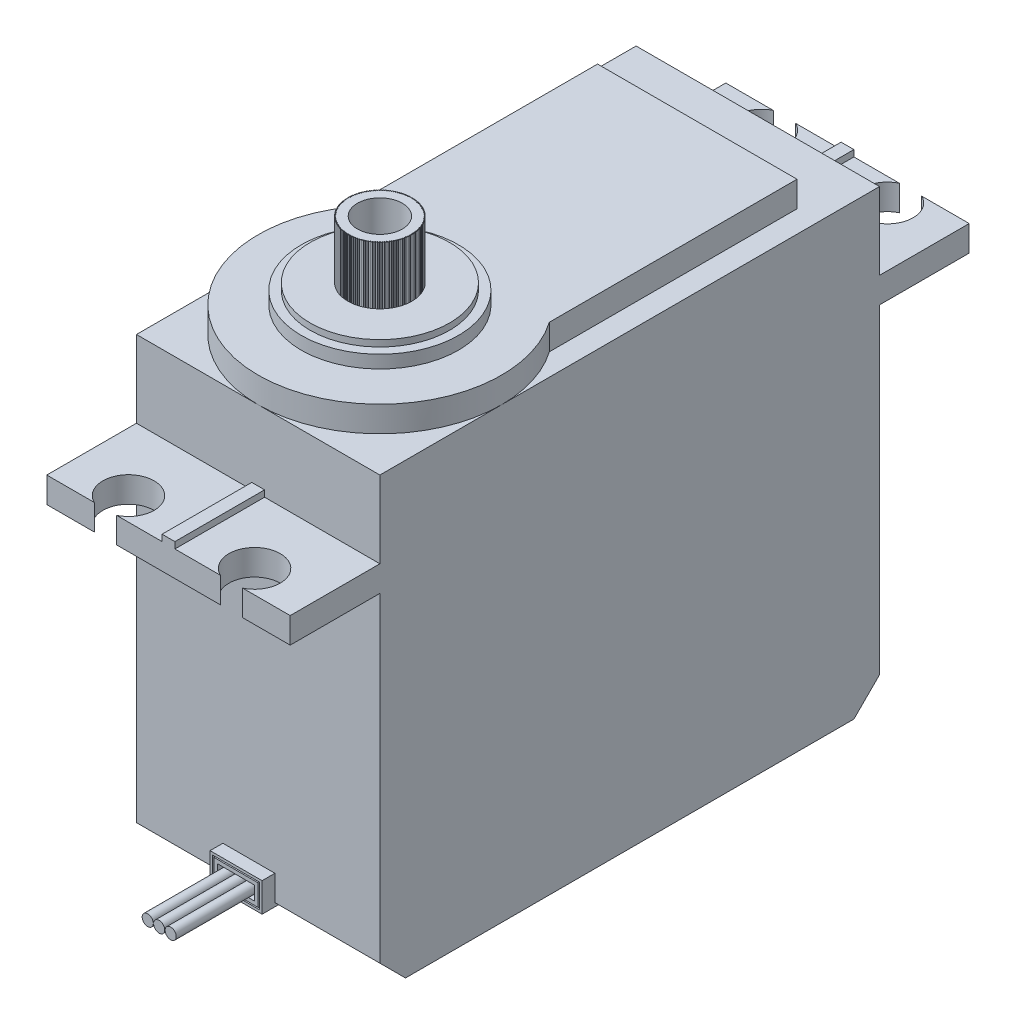
SolidWorks part; units mm, degrees
material "ABS PC"
ref_plane "Front Plane" through (0, 0, 0) normal (0, 0, 1) x (1, 0, 0)
ref_plane "Top Plane" through (0, 0, 0) normal (0, 1, 0) x (1, 0, 0)
ref_plane "Right Plane" through (0, 0, 0) normal (1, 0, 0) x (0, 0, -1)
sketch "Sketch1" plane through (0, 0, 0) normal (0, 1, 0) x (1, 0, 0)
  line L0 (0, 0) -> (19, 0)
  line L1 (19, 0) -> (19, 39)
  line L2 (19, 39) -> (0, 39)
  line L3 (0, 39) -> (0, 0)
  dimension "D1" = 19
  dimension "D2" = 39
extrude "Boss-Extrude1" add sketch "Sketch1" along normal blind 35
sketch "Sketch2" plane through (0, 35, 0) normal (0, 1, 0) x (1, 0, 0)
  line L0 (0, 39) -> (0, 0) construction
  line L2 (17.2849, 14.9447) -> (17.2849, 34.2756)
  line L3 (17.2849, 34.2756) -> (1.7151, 34.2756)
  line L5 (1.7151, 14.9447) -> (1.7151, 34.2756)
  circle A0 centre (9.5, 9.5) radius 1.75
  circle A1 centre (9.5, 9.5) radius 2.5
  circle A2 centre (9.5, 9.5) radius 9.5
  circle A3 centre (9.5, 9.5) radius 6.134
  circle A4 centre (9.5, 9.5) radius 5.4447
  dimension "D2" = 3.5
  dimension "D3" = 5
  dimension "D4" = 12.2681
  dimension "D1" = 10.8894
  dimension "D5" = 19
  dimension "D6" = 1.7151
  dimension "D7" = 9.5
  dimension "D8" = 9.5
  dimension "D10" = 34.2756
extrude "Boss-Extrude2" add sketch "Sketch2" along normal blind 2 contours A2 L2 L3 L5 | A2 A3 region at (9.5, 35, -25.9923) region at (18.3048, 35, -12.2735)
extrude "Boss-Extrude3" add sketch "Sketch2<4>" along normal blind 3 contours A3 A4 region at (3.5394, 35, -9.5)
sketch "Sketch2<4>" plane through (0, 35, 0) normal (0, 1, 0) x (1, 0, 0) same geometry as "Sketch2"
extrude "Boss-Extrude4" add sketch "Sketch2<5>" along normal blind 3.5 contours A4 A1 region at (4.2093, 35, -9.5)
sketch "Sketch2<5>" plane through (0, 35, 0) normal (0, 1, 0) x (1, 0, 0) same geometry as "Sketch2"
extrude "Boss-Extrude5" add sketch "Sketch2<6>" along normal blind 8 contours A1 A0 region at (7.0707, 35, -9.5)
sketch "Sketch2<6>" plane through (0, 35, 0) normal (0, 1, 0) x (1, 0, 0) same geometry as "Sketch2"
ref_plane "Plane1" through (0, 27, 0) normal (0, 1, 0) x (1, 0, 0)
sketch "Sketch3" plane through (0, 27, 0) normal (0, 1, 0) x (1, 0, 0)
  line L0 (0, 39) -> (19, 39)
  line L1 (19, 39) -> (19, 46)
  line L2 (19, 46) -> (15.2942, 46)
  line L3 (0, 46) -> (0, 39)
  line L4 (0, 0) -> (19, 0)
  line L5 (13.5465, 46) -> (5.4535, 46)
  line L6 (3.7058, 46) -> (0, 46)
  line L7 (0, 39) -> (0, 19.5)
  line L8 (0, 39) -> (0, 9.5) construction
  line L9 (0, 19.5) -> (19, 19.5)
  line L10 (19, 9.5) -> (19, 39) construction
  line L11 (9.5, 46) -> (9, 46)
  line L12 (9, 46) -> (9, 39)
  line L13 (9, 39) -> (10, 39)
  line L14 (10, 39) -> (10, 46)
  line L15 (19, 0) -> (19, -7)
  line L16 (19, -7) -> (15.2942, -7)
  line L17 (10, 0) -> (10, -7)
  line L18 (9, -7) -> (9, 0)
  line L19 (13.5465, -7) -> (5.4535, -7)
  line L20 (3.7058, -7) -> (0, -7)
  line L21 (0, -7) -> (0, 0)
  arc A0 (13.5465, 46) -> (15.2942, 46) centre (14.4204, 44.201) ccw
  arc A1 (5.4535, 46) -> (3.7058, 46) centre (4.5796, 44.201) cw
  arc A2 (13.5465, -7) -> (15.2942, -7) centre (14.4204, -5.201) cw
  arc A3 (5.4535, -7) -> (3.7058, -7) centre (4.5796, -5.201) ccw
  point P7 (0, 0)
  dimension "D2" = 4
  dimension "D1" = 7
  dimension "D3" = 19.5
  dimension "D4" = 0.5
  dimension "D5" = 1
extrude "Boss-Extrude6" add sketch "Sketch3" along normal blind 2 contours A3 L19 L18 L4 L21 L20 | L19 A2 L16 L15 L4 L17 | A0 L5 L14 L0 L1 L2 | L5 A1 L6 L3 L0 L12 region at (4.4806, 27, -42.0949) region at (14.5194, 27, -42.0949) region at (4.4806, 27, 3.0949) region at (14.5194, 27, 3.0949)
extrude "Boss-Extrude7" add sketch "Sketch3<3>" along normal blind 2.5 contours L0 L14 L5 L12 | L19 L17 L4 L18 region at (9.5, 27, -42.5) region at (9.5, 27, 3.5)
sketch "Sketch3<3>" plane through (0, 27, 0) normal (0, 1, 0) x (1, 0, 0) same geometry as "Sketch3"
ref_plane "Plane2" through (0, 0, -7) normal (0, 0, 1) x (1, 0, 0)
sketch "Sketch5" plane through (0, 43, 0) normal (0, 1, 0) x (1, 0, 0)
  line L0 (9.5017, 7) -> (9.5017, 7.0748) construction
  line L1 (-6.6, 7) -> (6.6, 7) construction
  line L2 (9.5017, 7.0748) -> (9.4463, 7.0077)
  line L3 (9.5017, 7.0748) -> (9.5593, 7.0077)
  line L4 (9.3748, 7.078) -> (9.4288, 7.008)
  line L5 (9.3748, 7.078) -> (9.3159, 7.0139)
  line L6 (9.2482, 7.0879) -> (9.2985, 7.0151)
  line L7 (9.2482, 7.0879) -> (9.1861, 7.027)
  line L8 (9.1223, 7.1044) -> (9.1687, 7.0291)
  line L9 (9.1223, 7.1044) -> (9.0571, 7.0468)
  line L10 (8.9975, 7.1274) -> (9.0399, 7.0498)
  line L11 (8.9975, 7.1274) -> (8.9293, 7.0733)
  line L12 (8.874, 7.157) -> (8.9123, 7.0773)
  line L13 (8.874, 7.157) -> (8.8031, 7.1065)
  line L14 (8.7522, 7.1929) -> (8.7863, 7.1113)
  line L15 (8.7522, 7.1929) -> (8.6788, 7.1463)
  line L16 (8.6325, 7.2352) -> (8.6622, 7.152)
  line L17 (8.6325, 7.2352) -> (8.5567, 7.1925)
  line L18 (8.5152, 7.2837) -> (8.5405, 7.199)
  line L19 (8.5152, 7.2837) -> (8.4372, 7.245)
  line L20 (8.4005, 7.3383) -> (8.4214, 7.2524)
  line L21 (8.4005, 7.3383) -> (8.3207, 7.3037)
  line L22 (8.2889, 7.3988) -> (8.3052, 7.3119)
  line L23 (8.2889, 7.3988) -> (8.2073, 7.3684)
  line L24 (8.1806, 7.4651) -> (8.1924, 7.3775)
  line L25 (8.1806, 7.4651) -> (8.0976, 7.439)
  line L26 (8.0759, 7.5369) -> (8.0831, 7.4488)
  line L27 (8.0759, 7.5369) -> (7.9916, 7.5152)
  line L28 (7.9751, 7.6142) -> (7.9777, 7.5258)
  line L29 (7.9751, 7.6142) -> (7.8898, 7.5969)
  line L30 (7.8785, 7.6965) -> (7.8764, 7.6081)
  line L31 (7.8785, 7.6965) -> (7.7924, 7.6838)
  line L32 (7.7863, 7.7839) -> (7.7796, 7.6957)
  line L33 (7.7863, 7.7839) -> (7.6997, 7.7756)
  line L34 (7.6989, 7.8759) -> (7.6876, 7.7882)
  line L35 (7.6989, 7.8759) -> (7.6119, 7.8722)
  line L36 (7.6163, 7.9724) -> (7.6005, 7.8854)
  line L37 (7.6163, 7.9724) -> (7.5293, 7.9733)
  line L38 (7.539, 8.0731) -> (7.5186, 7.987)
  line L39 (7.539, 8.0731) -> (7.4521, 8.0785)
  line L40 (7.467, 8.1777) -> (7.4421, 8.0928)
  line L41 (7.467, 8.1777) -> (7.3805, 8.1876)
  line L42 (7.4006, 8.2859) -> (7.3713, 8.2025)
  line L43 (7.4006, 8.2859) -> (7.3148, 8.3003)
  line L44 (7.3399, 8.3974) -> (7.3063, 8.3156)
  line L45 (7.3399, 8.3974) -> (7.255, 8.4163)
  line L46 (7.2852, 8.512) -> (7.2473, 8.4321)
  line L47 (7.2852, 8.512) -> (7.2013, 8.5353)
  line L48 (7.2365, 8.6293) -> (7.1945, 8.5514)
  line L49 (7.2365, 8.6293) -> (7.154, 8.657)
  line L50 (7.194, 8.7489) -> (7.148, 8.6734)
  line L51 (7.194, 8.7489) -> (7.1131, 8.7809)
  line L52 (7.1579, 8.8706) -> (7.108, 8.7976)
  line L53 (7.1579, 8.8706) -> (7.0787, 8.9068)
  line L54 (7.1281, 8.9941) -> (7.0745, 8.9238)
  line L55 (7.1281, 8.9941) -> (7.051, 9.0343)
  line L56 (7.1049, 9.1189) -> (7.0477, 9.0515)
  line L57 (7.1049, 9.1189) -> (7.03, 9.1631)
  line L58 (7.0882, 9.2448) -> (7.0275, 9.1805)
  line L59 (7.0882, 9.2448) -> (7.0157, 9.2929)
  line L60 (7.0782, 9.3713) -> (7.0142, 9.3103)
  line L61 (7.0782, 9.3713) -> (7.0083, 9.4232)
  line L62 (7.0748, 9.4983) -> (7.0077, 9.4407)
  line L63 (7.0748, 9.4983) -> (7.0077, 9.5537)
  line L64 (7.078, 9.6252) -> (7.008, 9.5712)
  line L65 (7.078, 9.6252) -> (7.0139, 9.6841)
  line L66 (7.0879, 9.7518) -> (7.0151, 9.7015)
  line L67 (7.0879, 9.7518) -> (7.027, 9.8139)
  line L68 (7.1044, 9.8777) -> (7.0291, 9.8313)
  line L69 (7.1044, 9.8777) -> (7.0468, 9.9429)
  line L70 (7.1274, 10.0025) -> (7.0498, 9.9601)
  line L71 (7.1274, 10.0025) -> (7.0733, 10.0707)
  line L72 (7.157, 10.126) -> (7.0773, 10.0877)
  line L73 (7.157, 10.126) -> (7.1065, 10.1969)
  line L74 (7.1929, 10.2478) -> (7.1113, 10.2137)
  line L75 (7.1929, 10.2478) -> (7.1463, 10.3212)
  line L76 (7.2352, 10.3675) -> (7.152, 10.3378)
  line L77 (7.2352, 10.3675) -> (7.1925, 10.4433)
  line L78 (7.2837, 10.4848) -> (7.199, 10.4595)
  line L79 (7.2837, 10.4848) -> (7.245, 10.5628)
  line L80 (7.3383, 10.5995) -> (7.2524, 10.5786)
  line L81 (7.3383, 10.5995) -> (7.3037, 10.6793)
  line L82 (7.3988, 10.7111) -> (7.3119, 10.6948)
  line L83 (7.3988, 10.7111) -> (7.3684, 10.7927)
  line L84 (7.4651, 10.8194) -> (7.3775, 10.8076)
  line L85 (7.4651, 10.8194) -> (7.439, 10.9024)
  line L86 (7.5369, 10.9241) -> (7.4488, 10.9169)
  line L87 (7.5369, 10.9241) -> (7.5152, 11.0084)
  line L88 (7.6142, 11.0249) -> (7.5258, 11.0223)
  line L89 (7.6142, 11.0249) -> (7.5969, 11.1102)
  line L90 (7.6965, 11.1215) -> (7.6081, 11.1236)
  line L91 (7.6965, 11.1215) -> (7.6838, 11.2076)
  line L92 (7.7839, 11.2137) -> (7.6957, 11.2204)
  line L93 (7.7839, 11.2137) -> (7.7756, 11.3003)
  line L94 (7.8759, 11.3011) -> (7.7882, 11.3124)
  line L95 (7.8759, 11.3011) -> (7.8722, 11.3881)
  line L96 (7.9724, 11.3837) -> (7.8854, 11.3995)
  line L97 (7.9724, 11.3837) -> (7.9733, 11.4707)
  line L98 (8.0731, 11.461) -> (7.987, 11.4814)
  line L99 (8.0731, 11.461) -> (8.0785, 11.5479)
  line L100 (8.1777, 11.533) -> (8.0928, 11.5579)
  line L101 (8.1777, 11.533) -> (8.1876, 11.6195)
  line L102 (8.2859, 11.5994) -> (8.2025, 11.6287)
  line L103 (8.2859, 11.5994) -> (8.3003, 11.6852)
  line L104 (8.3974, 11.6601) -> (8.3156, 11.6937)
  line L105 (8.3974, 11.6601) -> (8.4163, 11.745)
  line L106 (8.512, 11.7148) -> (8.4321, 11.7527)
  line L107 (8.512, 11.7148) -> (8.5353, 11.7987)
  line L108 (8.6293, 11.7635) -> (8.5514, 11.8055)
  line L109 (8.6293, 11.7635) -> (8.657, 11.846)
  line L110 (8.7489, 11.806) -> (8.6734, 11.852)
  line L111 (8.7489, 11.806) -> (8.7809, 11.8869)
  line L112 (8.8706, 11.8421) -> (8.7976, 11.892)
  line L113 (8.8706, 11.8421) -> (8.9068, 11.9213)
  line L114 (8.9941, 11.8719) -> (8.9238, 11.9255)
  line L115 (8.9941, 11.8719) -> (9.0343, 11.949)
  line L116 (9.1189, 11.8951) -> (9.0515, 11.9523)
  line L117 (9.1189, 11.8951) -> (9.1631, 11.97)
  line L118 (9.2448, 11.9118) -> (9.1805, 11.9725)
  line L119 (9.2448, 11.9118) -> (9.2929, 11.9843)
  line L120 (9.3713, 11.9218) -> (9.3103, 11.9858)
  line L121 (9.3713, 11.9218) -> (9.4232, 11.9917)
  line L122 (9.4983, 11.9252) -> (9.4407, 11.9923)
  line L123 (9.4983, 11.9252) -> (9.5537, 11.9923)
  line L124 (9.6252, 11.922) -> (9.5712, 11.992)
  line L125 (9.6252, 11.922) -> (9.6841, 11.9861)
  line L126 (9.7518, 11.9121) -> (9.7015, 11.9849)
  line L127 (9.7518, 11.9121) -> (9.8139, 11.973)
  line L128 (9.8777, 11.8956) -> (9.8313, 11.9709)
  line L129 (9.8777, 11.8956) -> (9.9429, 11.9532)
  line L130 (10.0025, 11.8726) -> (9.9601, 11.9502)
  line L131 (10.0025, 11.8726) -> (10.0707, 11.9267)
  line L132 (10.126, 11.843) -> (10.0877, 11.9227)
  line L133 (10.126, 11.843) -> (10.1969, 11.8935)
  line L134 (10.2478, 11.8071) -> (10.2137, 11.8887)
  line L135 (10.2478, 11.8071) -> (10.3212, 11.8537)
  line L136 (10.3675, 11.7648) -> (10.3378, 11.848)
  line L137 (10.3675, 11.7648) -> (10.4433, 11.8075)
  line L138 (10.4848, 11.7163) -> (10.4595, 11.801)
  line L139 (10.4848, 11.7163) -> (10.5628, 11.755)
  line L140 (10.5995, 11.6617) -> (10.5786, 11.7476)
  line L141 (10.5995, 11.6617) -> (10.6793, 11.6963)
  line L142 (10.7111, 11.6012) -> (10.6948, 11.6881)
  line L143 (10.7111, 11.6012) -> (10.7927, 11.6316)
  line L144 (10.8194, 11.5349) -> (10.8076, 11.6225)
  line L145 (10.8194, 11.5349) -> (10.9024, 11.561)
  line L146 (10.9241, 11.4631) -> (10.9169, 11.5512)
  line L147 (10.9241, 11.4631) -> (11.0084, 11.4848)
  line L148 (11.0249, 11.3858) -> (11.0223, 11.4742)
  line L149 (11.0249, 11.3858) -> (11.1102, 11.4031)
  line L150 (11.1215, 11.3035) -> (11.1236, 11.3919)
  line L151 (11.1215, 11.3035) -> (11.2076, 11.3162)
  line L152 (11.2137, 11.2161) -> (11.2204, 11.3043)
  line L153 (11.2137, 11.2161) -> (11.3003, 11.2244)
  line L154 (11.3011, 11.1241) -> (11.3124, 11.2118)
  line L155 (11.3011, 11.1241) -> (11.3881, 11.1278)
  line L156 (11.3837, 11.0276) -> (11.3995, 11.1146)
  line L157 (11.3837, 11.0276) -> (11.4707, 11.0267)
  line L158 (11.461, 10.9269) -> (11.4814, 11.013)
  line L159 (11.461, 10.9269) -> (11.5479, 10.9215)
  line L160 (11.533, 10.8223) -> (11.5579, 10.9072)
  line L161 (11.533, 10.8223) -> (11.6195, 10.8124)
  line L162 (11.5994, 10.7141) -> (11.6287, 10.7975)
  line L163 (11.5994, 10.7141) -> (11.6852, 10.6997)
  line L164 (11.6601, 10.6026) -> (11.6937, 10.6844)
  line L165 (11.6601, 10.6026) -> (11.745, 10.5837)
  line L166 (11.7148, 10.488) -> (11.7527, 10.5679)
  line L167 (11.7148, 10.488) -> (11.7987, 10.4647)
  line L168 (11.7635, 10.3707) -> (11.8055, 10.4486)
  line L169 (11.7635, 10.3707) -> (11.846, 10.343)
  line L170 (11.806, 10.2511) -> (11.852, 10.3266)
  line L171 (11.806, 10.2511) -> (11.8869, 10.2191)
  line L172 (11.8421, 10.1294) -> (11.892, 10.2024)
  line L173 (11.8421, 10.1294) -> (11.9213, 10.0932)
  line L174 (11.8719, 10.0059) -> (11.9255, 10.0762)
  line L175 (11.8719, 10.0059) -> (11.949, 9.9657)
  line L176 (11.8951, 9.8811) -> (11.9523, 9.9485)
  line L177 (11.8951, 9.8811) -> (11.97, 9.8369)
  line L178 (11.9118, 9.7552) -> (11.9725, 9.8195)
  line L179 (11.9118, 9.7552) -> (11.9843, 9.7071)
  line L180 (11.9218, 9.6287) -> (11.9858, 9.6897)
  line L181 (11.9218, 9.6287) -> (11.9917, 9.5768)
  line L182 (11.9252, 9.5017) -> (11.9923, 9.5593)
  line L183 (11.9252, 9.5017) -> (11.9923, 9.4463)
  line L184 (11.922, 9.3748) -> (11.992, 9.4288)
  line L185 (11.922, 9.3748) -> (11.9861, 9.3159)
  line L186 (11.9121, 9.2482) -> (11.9849, 9.2985)
  line L187 (11.9121, 9.2482) -> (11.973, 9.1861)
  line L188 (11.8956, 9.1223) -> (11.9709, 9.1687)
  line L189 (11.8956, 9.1223) -> (11.9532, 9.0571)
  line L190 (11.8726, 8.9975) -> (11.9502, 9.0399)
  line L191 (11.8726, 8.9975) -> (11.9267, 8.9293)
  line L192 (11.843, 8.874) -> (11.9227, 8.9123)
  line L193 (11.843, 8.874) -> (11.8935, 8.8031)
  line L194 (11.8071, 8.7522) -> (11.8887, 8.7863)
  line L195 (11.8071, 8.7522) -> (11.8537, 8.6788)
  line L196 (11.7648, 8.6325) -> (11.848, 8.6622)
  line L197 (11.7648, 8.6325) -> (11.8075, 8.5567)
  line L198 (11.7163, 8.5152) -> (11.801, 8.5405)
  line L199 (11.7163, 8.5152) -> (11.755, 8.4372)
  line L200 (11.6617, 8.4005) -> (11.7476, 8.4214)
  line L201 (11.6617, 8.4005) -> (11.6963, 8.3207)
  line L202 (11.6012, 8.2889) -> (11.6881, 8.3052)
  line L203 (11.6012, 8.2889) -> (11.6316, 8.2073)
  line L204 (11.5349, 8.1806) -> (11.6225, 8.1924)
  line L205 (11.5349, 8.1806) -> (11.561, 8.0976)
  line L206 (11.4631, 8.0759) -> (11.5512, 8.0831)
  line L207 (11.4631, 8.0759) -> (11.4848, 7.9916)
  line L208 (11.3858, 7.9751) -> (11.4742, 7.9777)
  line L209 (11.3858, 7.9751) -> (11.4031, 7.8898)
  line L210 (11.3035, 7.8785) -> (11.3919, 7.8764)
  line L211 (11.3035, 7.8785) -> (11.3162, 7.7924)
  line L212 (11.2161, 7.7863) -> (11.3043, 7.7796)
  line L213 (11.2161, 7.7863) -> (11.2244, 7.6997)
  line L214 (11.1241, 7.6989) -> (11.2118, 7.6876)
  line L215 (11.1241, 7.6989) -> (11.1278, 7.6119)
  line L216 (11.0276, 7.6163) -> (11.1146, 7.6005)
  line L217 (11.0276, 7.6163) -> (11.0267, 7.5293)
  line L218 (10.9269, 7.539) -> (11.013, 7.5186)
  line L219 (10.9269, 7.539) -> (10.9215, 7.4521)
  line L220 (10.8223, 7.467) -> (10.9072, 7.4421)
  line L221 (10.8223, 7.467) -> (10.8124, 7.3805)
  line L222 (10.7141, 7.4006) -> (10.7975, 7.3713)
  line L223 (10.7141, 7.4006) -> (10.6997, 7.3148)
  line L224 (10.6026, 7.3399) -> (10.6844, 7.3063)
  line L225 (10.6026, 7.3399) -> (10.5837, 7.255)
  line L226 (10.488, 7.2852) -> (10.5679, 7.2473)
  line L227 (10.488, 7.2852) -> (10.4647, 7.2013)
  line L228 (10.3707, 7.2365) -> (10.4486, 7.1945)
  line L229 (10.3707, 7.2365) -> (10.343, 7.154)
  line L230 (10.2511, 7.194) -> (10.3266, 7.148)
  line L231 (10.2511, 7.194) -> (10.2191, 7.1131)
  line L232 (10.1294, 7.1579) -> (10.2024, 7.108)
  line L233 (10.1294, 7.1579) -> (10.0932, 7.0787)
  line L234 (10.0059, 7.1281) -> (10.0762, 7.0745)
  line L235 (10.0059, 7.1281) -> (9.9657, 7.051)
  line L236 (9.8811, 7.1049) -> (9.9485, 7.0477)
  line L237 (9.8811, 7.1049) -> (9.8369, 7.03)
  line L238 (9.7552, 7.0882) -> (9.8195, 7.0275)
  line L239 (9.7552, 7.0882) -> (9.7071, 7.0157)
  line L240 (9.6287, 7.0782) -> (9.6897, 7.0142)
  line L241 (9.6287, 7.0782) -> (9.5768, 7.0083)
  line L242 (9.5, 9.5) -> (9.5028, 7.2027) construction
  arc A0 (9.5593, 7.0077) -> (9.4463, 7.0077) centre (9.5028, 7.2027) cw
  arc A1 (9.4288, 7.008) -> (9.3159, 7.0139) centre (9.3826, 7.2057) cw
  arc A2 (9.2985, 7.0151) -> (9.1861, 7.027) centre (9.2627, 7.215) cw
  arc A3 (9.1687, 7.0291) -> (9.0571, 7.0468) centre (9.1434, 7.2305) cw
  arc A4 (9.0399, 7.0498) -> (8.9293, 7.0733) centre (9.0251, 7.2523) cw
  arc A5 (8.9123, 7.0773) -> (8.8031, 7.1065) centre (8.9081, 7.2802) cw
  arc A6 (8.7863, 7.1113) -> (8.6788, 7.1463) centre (8.7928, 7.3143) cw
  arc A7 (8.6622, 7.152) -> (8.5567, 7.1925) centre (8.6794, 7.3543) cw
  arc A8 (8.5405, 7.199) -> (8.4372, 7.245) centre (8.5682, 7.4001) cw
  arc A9 (8.4214, 7.2524) -> (8.3207, 7.3037) centre (8.4596, 7.4518) cw
  arc A10 (8.3052, 7.3119) -> (8.2073, 7.3684) centre (8.3538, 7.5091) cw
  arc A11 (8.1924, 7.3775) -> (8.0976, 7.439) centre (8.2512, 7.5718) cw
  arc A12 (8.0831, 7.4488) -> (7.9916, 7.5152) centre (8.152, 7.6398) cw
  arc A13 (7.9777, 7.5258) -> (7.8898, 7.5969) centre (8.0565, 7.7129) cw
  arc A14 (7.8764, 7.6081) -> (7.7924, 7.6838) centre (7.9649, 7.7909) cw
  arc A15 (7.7796, 7.6957) -> (7.6997, 7.7756) centre (7.8776, 7.8736) cw
  arc A16 (7.6876, 7.7882) -> (7.6119, 7.8722) centre (7.7947, 7.9607) cw
  arc A17 (7.6005, 7.8854) -> (7.5293, 7.9733) centre (7.7164, 8.0521) cw
  arc A18 (7.5186, 7.987) -> (7.4521, 8.0785) centre (7.6431, 8.1474) cw
  arc A19 (7.4421, 8.0928) -> (7.3805, 8.1876) centre (7.5748, 8.2464) cw
  arc A20 (7.3713, 8.2025) -> (7.3148, 8.3003) centre (7.5119, 8.3489) cw
  arc A21 (7.3063, 8.3156) -> (7.255, 8.4163) centre (7.4544, 8.4545) cw
  arc A22 (7.2473, 8.4321) -> (7.2013, 8.5353) centre (7.4024, 8.563) cw
  arc A23 (7.1945, 8.5514) -> (7.154, 8.657) centre (7.3563, 8.6741) cw
  arc A24 (7.148, 8.6734) -> (7.1131, 8.7809) centre (7.316, 8.7874) cw
  arc A25 (7.108, 8.7976) -> (7.0787, 8.9068) centre (7.2817, 8.9027) cw
  arc A26 (7.0745, 8.9238) -> (7.051, 9.0343) centre (7.2535, 9.0196) cw
  arc A27 (7.0477, 9.0515) -> (7.03, 9.1631) centre (7.2314, 9.1378) cw
  arc A28 (7.0275, 9.1805) -> (7.0157, 9.2929) centre (7.2156, 9.2571) cw
  arc A29 (7.0142, 9.3103) -> (7.0083, 9.4232) centre (7.206, 9.3769) cw
  arc A30 (7.0077, 9.4407) -> (7.0077, 9.5537) centre (7.2027, 9.4972) cw
  arc A31 (7.008, 9.5712) -> (7.0139, 9.6841) centre (7.2057, 9.6174) cw
  arc A32 (7.0151, 9.7015) -> (7.027, 9.8139) centre (7.215, 9.7373) cw
  arc A33 (7.0291, 9.8313) -> (7.0468, 9.9429) centre (7.2305, 9.8566) cw
  arc A34 (7.0498, 9.9601) -> (7.0733, 10.0707) centre (7.2523, 9.9749) cw
  arc A35 (7.0773, 10.0877) -> (7.1065, 10.1969) centre (7.2802, 10.0919) cw
  arc A36 (7.1113, 10.2137) -> (7.1463, 10.3212) centre (7.3143, 10.2072) cw
  arc A37 (7.152, 10.3378) -> (7.1925, 10.4433) centre (7.3543, 10.3206) cw
  arc A38 (7.199, 10.4595) -> (7.245, 10.5628) centre (7.4001, 10.4318) cw
  arc A39 (7.2524, 10.5786) -> (7.3037, 10.6793) centre (7.4518, 10.5404) cw
  arc A40 (7.3119, 10.6948) -> (7.3684, 10.7927) centre (7.5091, 10.6462) cw
  arc A41 (7.3775, 10.8076) -> (7.439, 10.9024) centre (7.5718, 10.7488) cw
  arc A42 (7.4488, 10.9169) -> (7.5152, 11.0084) centre (7.6398, 10.848) cw
  arc A43 (7.5258, 11.0223) -> (7.5969, 11.1102) centre (7.7129, 10.9435) cw
  arc A44 (7.6081, 11.1236) -> (7.6838, 11.2076) centre (7.7909, 11.0351) cw
  arc A45 (7.6957, 11.2204) -> (7.7756, 11.3003) centre (7.8736, 11.1224) cw
  arc A46 (7.7882, 11.3124) -> (7.8722, 11.3881) centre (7.9607, 11.2053) cw
  arc A47 (7.8854, 11.3995) -> (7.9733, 11.4707) centre (8.0521, 11.2836) cw
  arc A48 (7.987, 11.4814) -> (8.0785, 11.5479) centre (8.1474, 11.3569) cw
  arc A49 (8.0928, 11.5579) -> (8.1876, 11.6195) centre (8.2464, 11.4252) cw
  arc A50 (8.2025, 11.6287) -> (8.3003, 11.6852) centre (8.3489, 11.4881) cw
  arc A51 (8.3156, 11.6937) -> (8.4163, 11.745) centre (8.4545, 11.5456) cw
  arc A52 (8.4321, 11.7527) -> (8.5353, 11.7987) centre (8.563, 11.5976) cw
  arc A53 (8.5514, 11.8055) -> (8.657, 11.846) centre (8.6741, 11.6437) cw
  arc A54 (8.6734, 11.852) -> (8.7809, 11.8869) centre (8.7874, 11.684) cw
  arc A55 (8.7976, 11.892) -> (8.9068, 11.9213) centre (8.9027, 11.7183) cw
  arc A56 (8.9238, 11.9255) -> (9.0343, 11.949) centre (9.0196, 11.7465) cw
  arc A57 (9.0515, 11.9523) -> (9.1631, 11.97) centre (9.1378, 11.7686) cw
  arc A58 (9.1805, 11.9725) -> (9.2929, 11.9843) centre (9.2571, 11.7844) cw
  arc A59 (9.3103, 11.9858) -> (9.4232, 11.9917) centre (9.3769, 11.794) cw
  arc A60 (9.4407, 11.9923) -> (9.5537, 11.9923) centre (9.4972, 11.7973) cw
  arc A61 (9.5712, 11.992) -> (9.6841, 11.9861) centre (9.6174, 11.7943) cw
  arc A62 (9.7015, 11.9849) -> (9.8139, 11.973) centre (9.7373, 11.785) cw
  arc A63 (9.8313, 11.9709) -> (9.9429, 11.9532) centre (9.8566, 11.7695) cw
  arc A64 (9.9601, 11.9502) -> (10.0707, 11.9267) centre (9.9749, 11.7477) cw
  arc A65 (10.0877, 11.9227) -> (10.1969, 11.8935) centre (10.0919, 11.7198) cw
  arc A66 (10.2137, 11.8887) -> (10.3212, 11.8537) centre (10.2072, 11.6857) cw
  arc A67 (10.3378, 11.848) -> (10.4433, 11.8075) centre (10.3206, 11.6457) cw
  arc A68 (10.4595, 11.801) -> (10.5628, 11.755) centre (10.4318, 11.5999) cw
  arc A69 (10.5786, 11.7476) -> (10.6793, 11.6963) centre (10.5404, 11.5482) cw
  arc A70 (10.6948, 11.6881) -> (10.7927, 11.6316) centre (10.6462, 11.4909) cw
  arc A71 (10.8076, 11.6225) -> (10.9024, 11.561) centre (10.7488, 11.4282) cw
  arc A72 (10.9169, 11.5512) -> (11.0084, 11.4848) centre (10.848, 11.3602) cw
  arc A73 (11.0223, 11.4742) -> (11.1102, 11.4031) centre (10.9435, 11.2871) cw
  arc A74 (11.1236, 11.3919) -> (11.2076, 11.3162) centre (11.0351, 11.2091) cw
  arc A75 (11.2204, 11.3043) -> (11.3003, 11.2244) centre (11.1224, 11.1264) cw
  arc A76 (11.3124, 11.2118) -> (11.3881, 11.1278) centre (11.2053, 11.0393) cw
  arc A77 (11.3995, 11.1146) -> (11.4707, 11.0267) centre (11.2836, 10.9479) cw
  arc A78 (11.4814, 11.013) -> (11.5479, 10.9215) centre (11.3569, 10.8526) cw
  arc A79 (11.5579, 10.9072) -> (11.6195, 10.8124) centre (11.4252, 10.7536) cw
  arc A80 (11.6287, 10.7975) -> (11.6852, 10.6997) centre (11.4881, 10.6511) cw
  arc A81 (11.6937, 10.6844) -> (11.745, 10.5837) centre (11.5456, 10.5455) cw
  arc A82 (11.7527, 10.5679) -> (11.7987, 10.4647) centre (11.5976, 10.437) cw
  arc A83 (11.8055, 10.4486) -> (11.846, 10.343) centre (11.6437, 10.3259) cw
  arc A84 (11.852, 10.3266) -> (11.8869, 10.2191) centre (11.684, 10.2126) cw
  arc A85 (11.892, 10.2024) -> (11.9213, 10.0932) centre (11.7183, 10.0973) cw
  arc A86 (11.9255, 10.0762) -> (11.949, 9.9657) centre (11.7465, 9.9804) cw
  arc A87 (11.9523, 9.9485) -> (11.97, 9.8369) centre (11.7686, 9.8622) cw
  arc A88 (11.9725, 9.8195) -> (11.9843, 9.7071) centre (11.7844, 9.7429) cw
  arc A89 (11.9858, 9.6897) -> (11.9917, 9.5768) centre (11.794, 9.6231) cw
  arc A90 (11.9923, 9.5593) -> (11.9923, 9.4463) centre (11.7973, 9.5028) cw
  arc A91 (11.992, 9.4288) -> (11.9861, 9.3159) centre (11.7943, 9.3826) cw
  arc A92 (11.9849, 9.2985) -> (11.973, 9.1861) centre (11.785, 9.2627) cw
  arc A93 (11.9709, 9.1687) -> (11.9532, 9.0571) centre (11.7695, 9.1434) cw
  arc A94 (11.9502, 9.0399) -> (11.9267, 8.9293) centre (11.7477, 9.0251) cw
  arc A95 (11.9227, 8.9123) -> (11.8935, 8.8031) centre (11.7198, 8.9081) cw
  arc A96 (11.8887, 8.7863) -> (11.8537, 8.6788) centre (11.6857, 8.7928) cw
  arc A97 (11.848, 8.6622) -> (11.8075, 8.5567) centre (11.6457, 8.6794) cw
  arc A98 (11.801, 8.5405) -> (11.755, 8.4372) centre (11.5999, 8.5682) cw
  arc A99 (11.7476, 8.4214) -> (11.6963, 8.3207) centre (11.5482, 8.4596) cw
  arc A100 (11.6881, 8.3052) -> (11.6316, 8.2073) centre (11.4909, 8.3538) cw
  arc A101 (11.6225, 8.1924) -> (11.561, 8.0976) centre (11.4282, 8.2512) cw
  arc A102 (11.5512, 8.0831) -> (11.4848, 7.9916) centre (11.3602, 8.152) cw
  arc A103 (11.4742, 7.9777) -> (11.4031, 7.8898) centre (11.2871, 8.0565) cw
  arc A104 (11.3919, 7.8764) -> (11.3162, 7.7924) centre (11.2091, 7.9649) cw
  arc A105 (11.3043, 7.7796) -> (11.2244, 7.6997) centre (11.1264, 7.8776) cw
  arc A106 (11.2118, 7.6876) -> (11.1278, 7.6119) centre (11.0393, 7.7947) cw
  arc A107 (11.1146, 7.6005) -> (11.0267, 7.5293) centre (10.9479, 7.7164) cw
  arc A108 (11.013, 7.5186) -> (10.9215, 7.4521) centre (10.8526, 7.6431) cw
  arc A109 (10.9072, 7.4421) -> (10.8124, 7.3805) centre (10.7536, 7.5748) cw
  arc A110 (10.7975, 7.3713) -> (10.6997, 7.3148) centre (10.6511, 7.5119) cw
  arc A111 (10.6844, 7.3063) -> (10.5837, 7.255) centre (10.5455, 7.4544) cw
  arc A112 (10.5679, 7.2473) -> (10.4647, 7.2013) centre (10.437, 7.4024) cw
  arc A113 (10.4486, 7.1945) -> (10.343, 7.154) centre (10.3259, 7.3563) cw
  arc A114 (10.3266, 7.148) -> (10.2191, 7.1131) centre (10.2126, 7.316) cw
  arc A115 (10.2024, 7.108) -> (10.0932, 7.0787) centre (10.0973, 7.2817) cw
  arc A116 (10.0762, 7.0745) -> (9.9657, 7.051) centre (9.9804, 7.2535) cw
  arc A117 (9.9485, 7.0477) -> (9.8369, 7.03) centre (9.8622, 7.2314) cw
  arc A118 (9.8195, 7.0275) -> (9.7071, 7.0157) centre (9.7429, 7.2156) cw
  arc A119 (9.6897, 7.0142) -> (9.5768, 7.0083) centre (9.6231, 7.206) cw
  dimension "D1" = 120
  dimension "D2" = 2.2973
extrude "Cut-Extrude1" cut sketch "Sketch5" against normal blind 5
sketch "Sketch6" plane through (0, 0, 0) normal (0, 0, 1) x (1, 0, 0)
  line L12 (7.4453, 2.8473) -> (7.4453, 2.4127)
  line L13 (7.4453, 2.4127) -> (10.1055, 2.4127)
  line L14 (10.1055, 2.4127) -> (10.1055, 3.2819)
  line L15 (10.1055, 3.2819) -> (7.4453, 3.2819)
  line L16 (7.4453, 3.2819) -> (7.4453, 2.8473)
  line L17 (10.6055, 3.7819) -> (6.9453, 3.7819)
  line L18 (6.9453, 3.7819) -> (6.9453, 2.8473)
  line L19 (6.9453, 2.8473) -> (6.9453, 1.9127)
  line L20 (6.9453, 1.9127) -> (10.6055, 1.9127)
  line L21 (10.6055, 1.9127) -> (10.6055, 3.7819)
  line L22 (10.8055, 3.9819) -> (6.7453, 3.9819)
  line L23 (6.7453, 3.9819) -> (6.7453, 2.8473)
  line L24 (6.7453, 2.8473) -> (6.7453, 1.7127)
  line L25 (6.7453, 1.7127) -> (10.8055, 1.7127)
  line L26 (10.8055, 1.7127) -> (10.8055, 3.9819)
  circle A0 centre (8.7708, 2.8473) radius 0.4346
  circle A1 centre (9.6708, 2.8473) radius 0.4346
  circle A2 centre (7.8799, 2.8473) radius 0.4346
  dimension "D1" = 0.5
  dimension "D2" = 0.2
extrude "Boss-Extrude8" add sketch "Sketch6" along normal blind 1 contours L25 L26 L22 L23 L24 L21 L20 L19 L18 L17 region at (10.7589, 2.8473, 0)
extrude "Boss-Extrude9" add sketch "Sketch6<3>" along normal blind 1 draft 6 contours L20 L21 L17 L18 L19 L16 L15 L14 L13 L12 region at (10.5644, 2.8473, 0)
sketch "Sketch6<3>" plane through (0, 0, 0) normal (0, 0, 1) x (1, 0, 0) same geometry as "Sketch6"
extrude "Boss-Extrude10" add sketch "Sketch6<4>" along normal blind 7 contours A2 | A0 | A1 region at (7.8799, 2.8473, 0) region at (8.7708, 2.8473, 0) region at (9.6708, 2.8473, 0)
sketch "Sketch6<4>" plane through (0, 0, 0) normal (0, 0, 1) x (1, 0, 0) same geometry as "Sketch6"
chamfer "Chamfer1" distance 2 angle 45 2 edges at (9.5, 0, -39) (9.5, 0, 0)
